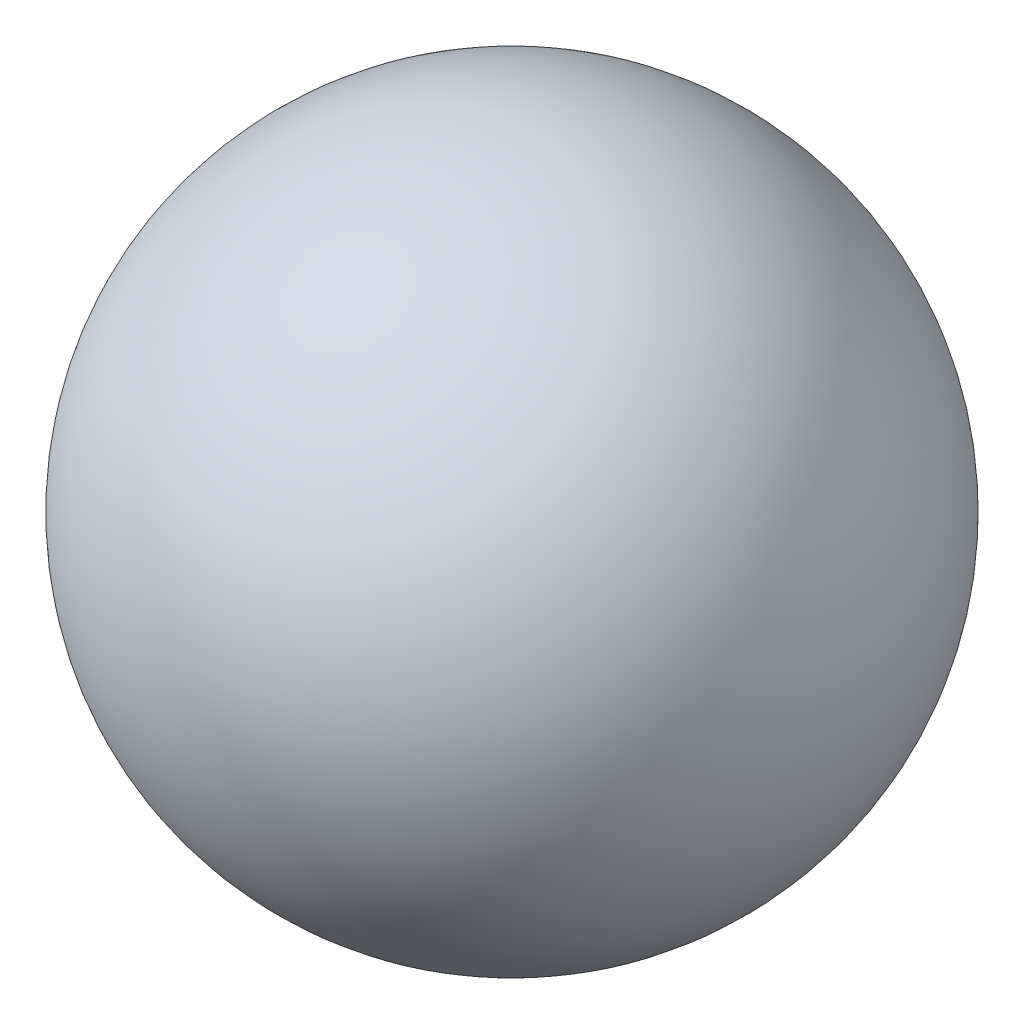
SolidWorks part; units mm, degrees
ref_plane "Front Plane" through (0, 0, 0) normal (0, 0, 1) x (1, 0, 0)
ref_plane "Top Plane" through (0, 0, 0) normal (0, 1, 0) x (1, 0, 0)
ref_plane "Right Plane" through (0, 0, 0) normal (1, 0, 0) x (0, 0, -1)
sketch "Sketch1" plane through (0, 0, 0) normal (0, 0, 1) x (1, 0, 0)
  line L0 (0, 0) -> (0, 45.5406) construction
  circle A0 centre (0, 0) radius 21.5
  dimension "D1" = 43
revolve "Revolve2" add sketch "Sketch1" angle 360 about L0 region at (-14.7728, -14.7728, 0)
sketch "Sketch2" plane through (0, 0, 0) normal (1, 0, 0) x (0, 0, -1)
  line L0 (0, 0) -> (0, 12.0099) construction
